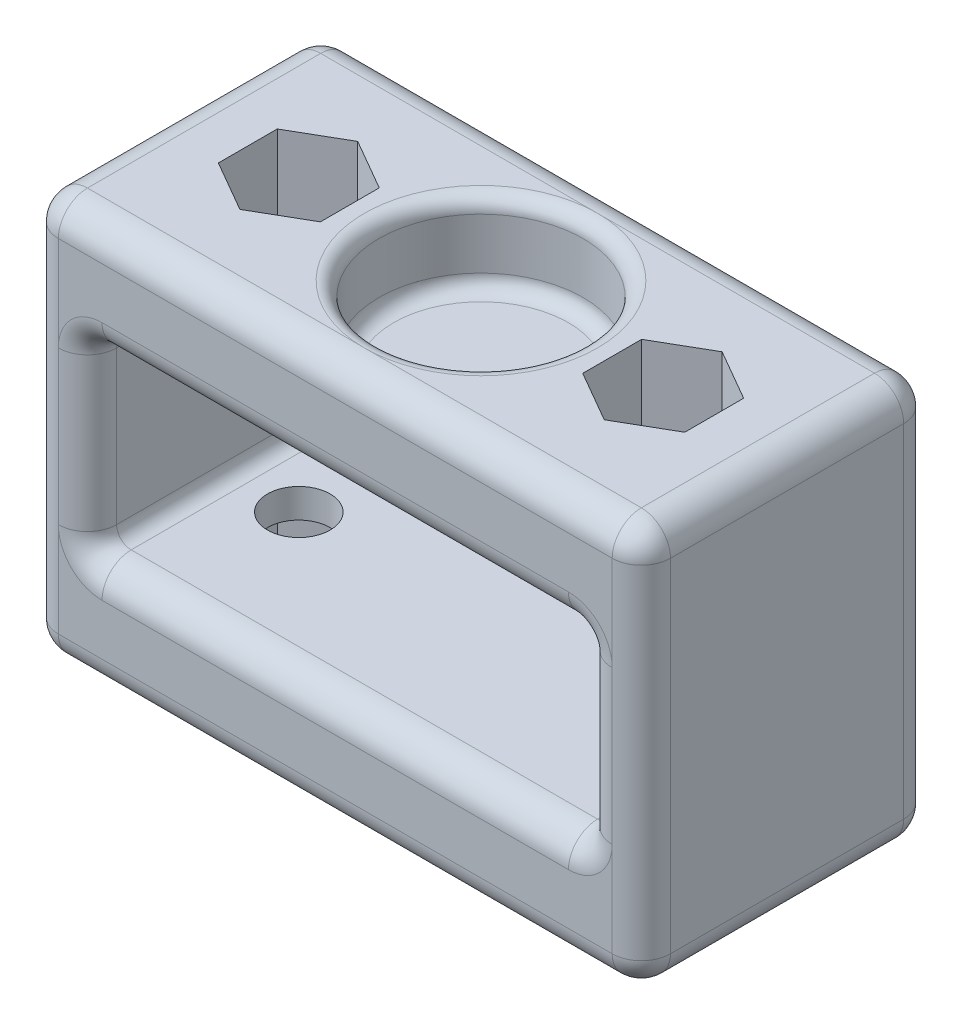
SolidWorks part; units mm, degrees
material "ABS"
ref_plane "前视基准面" through (0, 0, 0) normal (0, 0, 1) x (1, 0, 0)
ref_plane "上视基准面" through (0, 0, 0) normal (0, 1, 0) x (1, 0, 0)
ref_plane "右视基准面" through (0, 0, 0) normal (1, 0, 0) x (0, 0, -1)
sketch "草图1" plane through (0, 0, 0) normal (0, 0, 1) x (1, 0, 0)
  line L1 (21, -13.75) -> (-21, -13.75)
  line L2 (21, -13.75) -> (21, 13.75)
  line L3 (21, 13.75) -> (-21, 13.75)
  line L4 (-21, -13.75) -> (-21, 13.75)
  line L5 (0, 13.75) -> (0, 0) construction
  line L6 (0, 0) -> (-21, 0) construction
  dimension "D1" = 42
  dimension "D2" = 27.5
extrude "凸台-拉伸1" add sketch "草图1" along normal mid plane 20
sketch "草图2" plane through (0, 13.75, 0) normal (0, 1, 0) x (1, 0, 0)
  line L0 (-12.5, 0) -> (12.5, 0) construction
  circle A0 centre (-12.5, 0) radius 2.15
  circle A1 centre (12.5, 0) radius 2.15
  dimension "D2" = 4.3
  dimension "D1" = 25
extrude "切除-拉伸1" cut sketch "草图2" against normal through all and the other way through all
sketch "草图3" plane through (0, 13.75, 0) normal (0, 1, 0) x (1, 0, 0)
  line L0 (0, -11) -> (0, 11) construction
  line L1 (-9, -2.0207) -> (-9, 2.0207)
  line L2 (-9, 2.0207) -> (-12.5, 4.0415)
  line L3 (-12.5, 4.0415) -> (-16, 2.0207)
  line L4 (-16, 2.0207) -> (-16, -2.0207)
  line L5 (-16, -2.0207) -> (-12.5, -4.0415)
  line L6 (-12.5, -4.0415) -> (-9, -2.0207)
  line L7 (12.5, -4.0415) -> (9, -2.0207)
  line L8 (16, -2.0207) -> (12.5, -4.0415)
  line L9 (16, 2.0207) -> (16, -2.0207)
  line L10 (12.5, 4.0415) -> (16, 2.0207)
  line L11 (9, 2.0207) -> (12.5, 4.0415)
  line L12 (9, -2.0207) -> (9, 2.0207)
  circle A0 centre (-12.5, 0) radius 3.5 construction
  circle A1 centre (12.5, 0) radius 3.5 construction
  circle A2 centre (0, 0) radius 7
  dimension "D1" = 7
  dimension "D2" = 14
extrude "切除-拉伸2" cut sketch "草图3" against normal blind 5.5
mirror "镜向2" about plane through (0, 0, 0) normal (0, 1, 0) of "切除-拉伸2"
sketch "草图5" plane through (0, 0, 0) normal (0, 0, 1) x (1, 0, 0)
  line L1 (16, -6.25) -> (-16, -6.25)
  line L2 (17, -5.25) -> (17, 5.25)
  line L3 (16, 6.25) -> (-16, 6.25)
  line L4 (-17, -5.25) -> (-17, 5.25)
  line L5 (0, 6.25) -> (0, 0) construction
  line L6 (0, 0) -> (-17, 0) construction
  line L7 (-12.5, 8.25) -> (-9, 8.25) construction
  line L9 (-21, 13.75) -> (-21, -13.75) construction
  arc A0 (16, -6.25) -> (17, -5.25) centre (16, -5.25) ccw
  arc A1 (-16, -6.25) -> (-17, -5.25) centre (-16, -5.25) cw
  arc A2 (-16, 6.25) -> (-17, 5.25) centre (-16, 5.25) ccw
  arc A3 (17, 5.25) -> (16, 6.25) centre (16, 5.25) ccw
  dimension "D3" = 1
  dimension "D1" = 4
  dimension "D2" = 2
extrude "切除-拉伸4" cut sketch "草图5" against normal through all both and the other way through all
fillet "圆角1" radius 2 28 edges at (21, 0, 10) (21, 0, -10) (-21, 0, -10) (-21, 0, 10) (-16.7071, 5.9571, 10) (0, 6.25, 10) (16.7071, 5.9571, 10) (17, 0, 10) (16.7071, -5.9571, 10) (0, -6.25, 10) (-16.7071, -5.9571, 10) (-16.7071, 5.9571, -10) (0, 6.25, -10) (16.7071, 5.9571, -10) (17, 0, -10) (16.7071, -5.9571, -10) (0, -6.25, -10) (-16.7071, -5.9571, -10) (-17, 0, 10) (-17, 0, -10) (0, 13.75, 10) (0, -13.75, 10) (21, 13.75, 0) (0, 13.75, -10) (21, -13.75, 0) (0, -13.75, -10) (-21, -13.75, 0) (-21, 13.75, 0)
fillet "圆角3" radius 1 4 edges at (-7, -13.75, 0) (-7, 13.75, 0) (-7, -8.25, 0) (-7, 8.25, 0)
